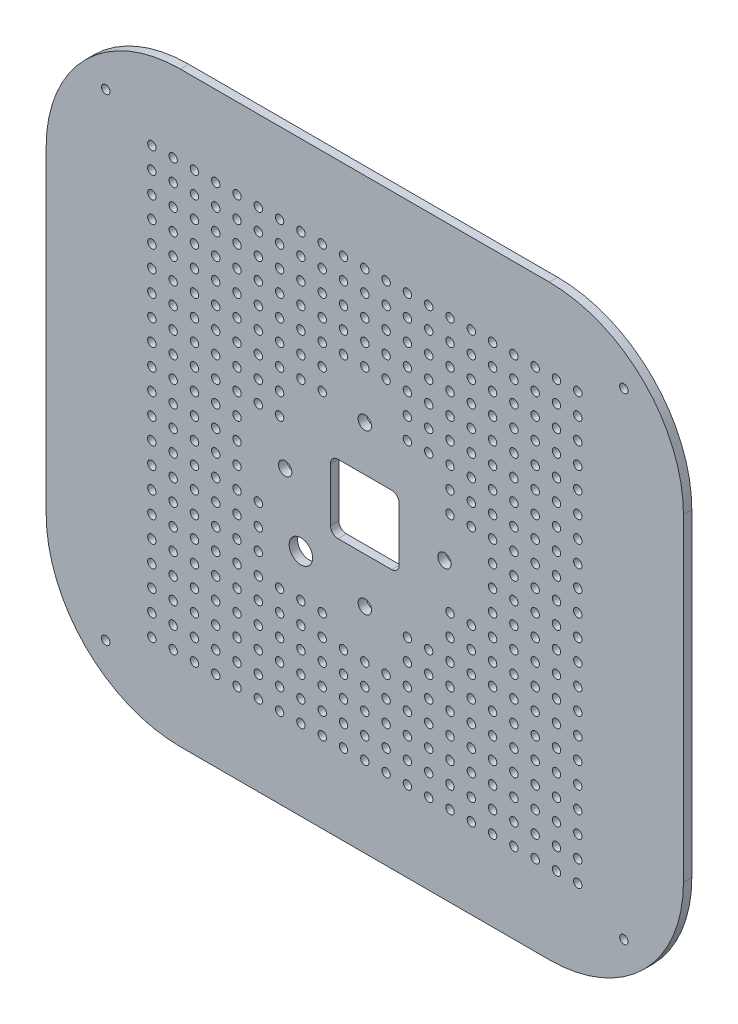
SolidWorks part; units mm, degrees
ref_plane "前视基准面" through (0, 0, 0) normal (0, 0, 1) x (1, 0, 0)
ref_plane "上视基准面" through (0, 0, 0) normal (0, 1, 0) x (1, 0, 0)
ref_plane "右视基准面" through (0, 0, 0) normal (1, 0, 0) x (0, 0, -1)
sketch "草图1" plane through (0, 0, 0) normal (0, 0, 1) x (1, 0, 0)
  line L0 (190, -61.2563) -> (190, 88.7437)
  line L2 (-190, 175) -> (-190, 88.7437)
  line L3 (-190, -175) -> (190, -175)
  line L4 (190, 175) -> (190, 88.7437)
  line L5 (-190, 175) -> (190, -175) construction
  line L6 (-190, -175) -> (190, 175) construction
  line L11 (-190, -61.2563) -> (-190, 88.7437)
  line L12 (-20.5, -20.5) -> (20.5, -20.5)
  line L17 (190, -61.2563) -> (190, -175)
  line L18 (-190, -61.2563) -> (-190, -175)
  line L19 (-20.5, -20.5) -> (-20.5, 20.5)
  line L20 (-20.5, 20.5) -> (20.5, 20.5)
  line L21 (20.5, -20.5) -> (20.5, 20.5)
  line L22 (-20.5, -20.5) -> (20.5, 20.5) construction
  line L23 (-20.5, 20.5) -> (20.5, -20.5) construction
  line L24 (190, 175) -> (-190, 175)
  circle A8 centre (154.4645, 142.2699) radius 2.5
  circle A10 centre (0, 0) radius 210 construction
  circle A13 centre (-154.4645, 142.2699) radius 2.5
  circle A14 centre (-154.4645, -142.2699) radius 2.5
  circle A15 centre (154.4645, -142.2699) radius 2.5
  point P0 (0, 0)
  point P56 (0, 0)
  dimension "D1" = 380
extrude "凸台-拉伸1" add sketch "草图1" along normal blind 5
fillet "圆角1" radius 80 4 edges at (-190, -175, 2.5) (190, -175, 2.5) (-190, 175, 2.5) (190, 175, 2.5)
fillet "圆角3" radius 4.5 4 edges at (-20.5, 20.5, 2.5) (20.5, 20.5, 2.5) (20.5, -20.5, 2.5) (-20.5, -20.5, 2.5)
sketch "草图2" plane through (0, 0, 5) normal (0, 0, 1) x (1, 0, 0)
  circle A0 centre (127, -127) radius 2.5
  circle A1 centre (114.3, -127) radius 2.5
  circle A2 centre (101.6, -127) radius 2.5
  circle A3 centre (88.9, -127) radius 2.5
  circle A4 centre (76.2, -127) radius 2.5
  circle A5 centre (63.5, -127) radius 2.5
  circle A6 centre (50.8, -127) radius 2.5
  circle A7 centre (38.1, -127) radius 2.5
  circle A8 centre (25.4, -127) radius 2.5
  circle A9 centre (12.7, -127) radius 2.5
  circle A10 centre (0, -127) radius 2.5
  circle A11 centre (-12.7, -127) radius 2.5
  circle A12 centre (-25.4, -127) radius 2.5
  circle A13 centre (-38.1, -127) radius 2.5
  circle A14 centre (-50.8, -127) radius 2.5
  circle A15 centre (-63.5, -127) radius 2.5
  circle A16 centre (-76.2, -127) radius 2.5
  circle A17 centre (-88.9, -127) radius 2.5
  circle A18 centre (-101.6, -127) radius 2.5
  circle A19 centre (-114.3, -127) radius 2.5
  circle A20 centre (114.3, -114.3) radius 2.5
  circle A21 centre (101.6, -114.3) radius 2.5
  circle A22 centre (88.9, -114.3) radius 2.5
  circle A23 centre (76.2, -114.3) radius 2.5
  circle A24 centre (63.5, -114.3) radius 2.5
  circle A25 centre (50.8, -114.3) radius 2.5
  circle A26 centre (38.1, -114.3) radius 2.5
  circle A27 centre (25.4, -114.3) radius 2.5
  circle A28 centre (12.7, -114.3) radius 2.5
  circle A29 centre (0, -114.3) radius 2.5
  circle A30 centre (-12.7, -114.3) radius 2.5
  circle A31 centre (-25.4, -114.3) radius 2.5
  circle A32 centre (-38.1, -114.3) radius 2.5
  circle A33 centre (-50.8, -114.3) radius 2.5
  circle A34 centre (-63.5, -114.3) radius 2.5
  circle A35 centre (-76.2, -114.3) radius 2.5
  circle A36 centre (-88.9, -114.3) radius 2.5
  circle A37 centre (-101.6, -114.3) radius 2.5
  circle A38 centre (-114.3, -114.3) radius 2.5
  circle A39 centre (114.3, -101.6) radius 2.5
  circle A40 centre (101.6, -101.6) radius 2.5
  circle A41 centre (88.9, -101.6) radius 2.5
  circle A42 centre (76.2, -101.6) radius 2.5
  circle A43 centre (63.5, -101.6) radius 2.5
  circle A44 centre (50.8, -101.6) radius 2.5
  circle A45 centre (38.1, -101.6) radius 2.5
  circle A46 centre (25.4, -101.6) radius 2.5
  circle A47 centre (12.7, -101.6) radius 2.5
  circle A48 centre (0, -101.6) radius 2.5
  circle A49 centre (-12.7, -101.6) radius 2.5
  circle A50 centre (-25.4, -101.6) radius 2.5
  circle A51 centre (-38.1, -101.6) radius 2.5
  circle A52 centre (-50.8, -101.6) radius 2.5
  circle A53 centre (-63.5, -101.6) radius 2.5
  circle A54 centre (-76.2, -101.6) radius 2.5
  circle A55 centre (-88.9, -101.6) radius 2.5
  circle A56 centre (-101.6, -101.6) radius 2.5
  circle A57 centre (-114.3, -101.6) radius 2.5
  circle A58 centre (114.3, -88.9) radius 2.5
  circle A59 centre (101.6, -88.9) radius 2.5
  circle A60 centre (88.9, -88.9) radius 2.5
  circle A61 centre (76.2, -88.9) radius 2.5
  circle A62 centre (63.5, -88.9) radius 2.5
  circle A63 centre (50.8, -88.9) radius 2.5
  circle A64 centre (38.1, -88.9) radius 2.5
  circle A65 centre (25.4, -88.9) radius 2.5
  circle A66 centre (12.7, -88.9) radius 2.5
  circle A67 centre (0, -88.9) radius 2.5
  circle A68 centre (-12.7, -88.9) radius 2.5
  circle A69 centre (-25.4, -88.9) radius 2.5
  circle A70 centre (-38.1, -88.9) radius 2.5
  circle A71 centre (-50.8, -88.9) radius 2.5
  circle A72 centre (-63.5, -88.9) radius 2.5
  circle A73 centre (-76.2, -88.9) radius 2.5
  circle A74 centre (-88.9, -88.9) radius 2.5
  circle A75 centre (-101.6, -88.9) radius 2.5
  circle A76 centre (-114.3, -88.9) radius 2.5
  circle A77 centre (114.3, -76.2) radius 2.5
  circle A78 centre (101.6, -76.2) radius 2.5
  circle A79 centre (88.9, -76.2) radius 2.5
  circle A80 centre (76.2, -76.2) radius 2.5
  circle A81 centre (63.5, -76.2) radius 2.5
  circle A82 centre (50.8, -76.2) radius 2.5
  circle A83 centre (38.1, -76.2) radius 2.5
  circle A84 centre (25.4, -76.2) radius 2.5
  circle A85 centre (12.7, -76.2) radius 2.5
  circle A86 centre (0, -76.2) radius 2.5
  circle A87 centre (-12.7, -76.2) radius 2.5
  circle A88 centre (-25.4, -76.2) radius 2.5
  circle A89 centre (-38.1, -76.2) radius 2.5
  circle A90 centre (-50.8, -76.2) radius 2.5
  circle A91 centre (-63.5, -76.2) radius 2.5
  circle A92 centre (-76.2, -76.2) radius 2.5
  circle A93 centre (-88.9, -76.2) radius 2.5
  circle A94 centre (-101.6, -76.2) radius 2.5
  circle A95 centre (-114.3, -76.2) radius 2.5
  circle A96 centre (114.3, -63.5) radius 2.5
  circle A97 centre (101.6, -63.5) radius 2.5
  circle A98 centre (88.9, -63.5) radius 2.5
  circle A99 centre (76.2, -63.5) radius 2.5
  circle A100 centre (63.5, -63.5) radius 2.5
  circle A101 centre (50.8, -63.5) radius 2.5
  circle A102 centre (38.1, -63.5) radius 2.5
  circle A103 centre (25.4, -63.5) radius 2.5
  circle A107 centre (-25.4, -63.5) radius 2.5
  circle A108 centre (-38.1, -63.5) radius 2.5
  circle A109 centre (-50.8, -63.5) radius 2.5
  circle A110 centre (-63.5, -63.5) radius 2.5
  circle A111 centre (-76.2, -63.5) radius 2.5
  circle A112 centre (-88.9, -63.5) radius 2.5
  circle A113 centre (-101.6, -63.5) radius 2.5
  circle A114 centre (-114.3, -63.5) radius 2.5
  circle A115 centre (114.3, -50.8) radius 2.5
  circle A116 centre (101.6, -50.8) radius 2.5
  circle A117 centre (88.9, -50.8) radius 2.5
  circle A118 centre (76.2, -50.8) radius 2.5
  circle A119 centre (63.5, -50.8) radius 2.5
  circle A120 centre (50.8, -50.8) radius 2.5
  circle A121 centre (38.1, -50.8) radius 2.5
  circle A122 centre (25.4, -50.8) radius 2.5
  circle A129 centre (-63.5, -50.8) radius 2.5
  circle A130 centre (-76.2, -50.8) radius 2.5
  circle A131 centre (-88.9, -50.8) radius 2.5
  circle A132 centre (-101.6, -50.8) radius 2.5
  circle A133 centre (-114.3, -50.8) radius 2.5
  circle A134 centre (114.3, -38.1) radius 2.5
  circle A135 centre (101.6, -38.1) radius 2.5
  circle A136 centre (88.9, -38.1) radius 2.5
  circle A137 centre (76.2, -38.1) radius 2.5
  circle A138 centre (63.5, -38.1) radius 2.5
  circle A139 centre (50.8, -38.1) radius 2.5
  circle A148 centre (-63.5, -38.1) radius 2.5
  circle A149 centre (-76.2, -38.1) radius 2.5
  circle A150 centre (-88.9, -38.1) radius 2.5
  circle A151 centre (-101.6, -38.1) radius 2.5
  circle A152 centre (-114.3, -38.1) radius 2.5
  circle A153 centre (114.3, -25.4) radius 2.5
  circle A154 centre (101.6, -25.4) radius 2.5
  circle A155 centre (88.9, -25.4) radius 2.5
  circle A156 centre (76.2, -25.4) radius 2.5
  circle A157 centre (63.5, -25.4) radius 2.5
  circle A158 centre (50.8, -25.4) radius 2.5
  circle A167 centre (-63.5, -25.4) radius 2.5
  circle A168 centre (-76.2, -25.4) radius 2.5
  circle A169 centre (-88.9, -25.4) radius 2.5
  circle A170 centre (-101.6, -25.4) radius 2.5
  circle A171 centre (-114.3, -25.4) radius 2.5
  circle A172 centre (114.3, -12.7) radius 2.5
  circle A173 centre (101.6, -12.7) radius 2.5
  circle A174 centre (88.9, -12.7) radius 2.5
  circle A175 centre (76.2, -12.7) radius 2.5
  circle A187 centre (-76.2, -12.7) radius 2.5
  circle A188 centre (-88.9, -12.7) radius 2.5
  circle A189 centre (-101.6, -12.7) radius 2.5
  circle A190 centre (-114.3, -12.7) radius 2.5
  circle A191 centre (114.3, 0) radius 2.5
  circle A192 centre (101.6, 0) radius 2.5
  circle A193 centre (88.9, 0) radius 2.5
  circle A194 centre (76.2, 0) radius 2.5
  circle A206 centre (-76.2, 0) radius 2.5
  circle A207 centre (-88.9, 0) radius 2.5
  circle A208 centre (-101.6, 0) radius 2.5
  circle A209 centre (-114.3, 0) radius 2.5
  circle A210 centre (114.3, 12.7) radius 2.5
  circle A211 centre (101.6, 12.7) radius 2.5
  circle A212 centre (88.9, 12.7) radius 2.5
  circle A213 centre (76.2, 12.7) radius 2.5
  circle A225 centre (-76.2, 12.7) radius 2.5
  circle A226 centre (-88.9, 12.7) radius 2.5
  circle A227 centre (-101.6, 12.7) radius 2.5
  circle A228 centre (-114.3, 12.7) radius 2.5
  circle A229 centre (114.3, 25.4) radius 2.5
  circle A230 centre (101.6, 25.4) radius 2.5
  circle A231 centre (88.9, 25.4) radius 2.5
  circle A232 centre (76.2, 25.4) radius 2.5
  circle A233 centre (63.5, 25.4) radius 2.5
  circle A234 centre (50.8, 25.4) radius 2.5
  circle A242 centre (-50.8, 25.4) radius 2.5
  circle A243 centre (-63.5, 25.4) radius 2.5
  circle A244 centre (-76.2, 25.4) radius 2.5
  circle A245 centre (-88.9, 25.4) radius 2.5
  circle A246 centre (-101.6, 25.4) radius 2.5
  circle A247 centre (-114.3, 25.4) radius 2.5
  circle A248 centre (114.3, 38.1) radius 2.5
  circle A249 centre (101.6, 38.1) radius 2.5
  circle A250 centre (88.9, 38.1) radius 2.5
  circle A251 centre (76.2, 38.1) radius 2.5
  circle A252 centre (63.5, 38.1) radius 2.5
  circle A253 centre (50.8, 38.1) radius 2.5
  circle A261 centre (-50.8, 38.1) radius 2.5
  circle A262 centre (-63.5, 38.1) radius 2.5
  circle A263 centre (-76.2, 38.1) radius 2.5
  circle A264 centre (-88.9, 38.1) radius 2.5
  circle A265 centre (-101.6, 38.1) radius 2.5
  circle A266 centre (-114.3, 38.1) radius 2.5
  circle A267 centre (114.3, 50.8) radius 2.5
  circle A268 centre (101.6, 50.8) radius 2.5
  circle A269 centre (88.9, 50.8) radius 2.5
  circle A270 centre (76.2, 50.8) radius 2.5
  circle A271 centre (63.5, 50.8) radius 2.5
  circle A272 centre (50.8, 50.8) radius 2.5
  circle A273 centre (38.1, 50.8) radius 2.5
  circle A274 centre (25.4, 50.8) radius 2.5
  circle A278 centre (-25.4, 50.8) radius 2.5
  circle A279 centre (-38.1, 50.8) radius 2.5
  circle A280 centre (-50.8, 50.8) radius 2.5
  circle A281 centre (-63.5, 50.8) radius 2.5
  circle A282 centre (-76.2, 50.8) radius 2.5
  circle A283 centre (-88.9, 50.8) radius 2.5
  circle A284 centre (-101.6, 50.8) radius 2.5
  circle A285 centre (-114.3, 50.8) radius 2.5
  circle A286 centre (114.3, 63.5) radius 2.5
  circle A287 centre (101.6, 63.5) radius 2.5
  circle A288 centre (88.9, 63.5) radius 2.5
  circle A289 centre (76.2, 63.5) radius 2.5
  circle A290 centre (63.5, 63.5) radius 2.5
  circle A291 centre (50.8, 63.5) radius 2.5
  circle A292 centre (38.1, 63.5) radius 2.5
  circle A293 centre (25.4, 63.5) radius 2.5
  circle A297 centre (-25.4, 63.5) radius 2.5
  circle A298 centre (-38.1, 63.5) radius 2.5
  circle A299 centre (-50.8, 63.5) radius 2.5
  circle A300 centre (-63.5, 63.5) radius 2.5
  circle A301 centre (-76.2, 63.5) radius 2.5
  circle A302 centre (-88.9, 63.5) radius 2.5
  circle A303 centre (-101.6, 63.5) radius 2.5
  circle A304 centre (-114.3, 63.5) radius 2.5
  circle A305 centre (114.3, 76.2) radius 2.5
  circle A306 centre (101.6, 76.2) radius 2.5
  circle A307 centre (88.9, 76.2) radius 2.5
  circle A308 centre (76.2, 76.2) radius 2.5
  circle A309 centre (63.5, 76.2) radius 2.5
  circle A310 centre (50.8, 76.2) radius 2.5
  circle A311 centre (38.1, 76.2) radius 2.5
  circle A312 centre (25.4, 76.2) radius 2.5
  circle A313 centre (12.7, 76.2) radius 2.5
  circle A314 centre (0, 76.2) radius 2.5
  circle A315 centre (-12.7, 76.2) radius 2.5
  circle A316 centre (-25.4, 76.2) radius 2.5
  circle A317 centre (-38.1, 76.2) radius 2.5
  circle A318 centre (-50.8, 76.2) radius 2.5
  circle A319 centre (-63.5, 76.2) radius 2.5
  circle A320 centre (-76.2, 76.2) radius 2.5
  circle A321 centre (-88.9, 76.2) radius 2.5
  circle A322 centre (-101.6, 76.2) radius 2.5
  circle A323 centre (-114.3, 76.2) radius 2.5
  circle A324 centre (114.3, 88.9) radius 2.5
  circle A325 centre (101.6, 88.9) radius 2.5
  circle A326 centre (88.9, 88.9) radius 2.5
  circle A327 centre (76.2, 88.9) radius 2.5
  circle A328 centre (63.5, 88.9) radius 2.5
  circle A329 centre (50.8, 88.9) radius 2.5
  circle A330 centre (38.1, 88.9) radius 2.5
  circle A331 centre (25.4, 88.9) radius 2.5
  circle A332 centre (12.7, 88.9) radius 2.5
  circle A333 centre (0, 88.9) radius 2.5
  circle A334 centre (-12.7, 88.9) radius 2.5
  circle A335 centre (-25.4, 88.9) radius 2.5
  circle A336 centre (-38.1, 88.9) radius 2.5
  circle A337 centre (-50.8, 88.9) radius 2.5
  circle A338 centre (-63.5, 88.9) radius 2.5
  circle A339 centre (-76.2, 88.9) radius 2.5
  circle A340 centre (-88.9, 88.9) radius 2.5
  circle A341 centre (-101.6, 88.9) radius 2.5
  circle A342 centre (-114.3, 88.9) radius 2.5
  circle A343 centre (114.3, 101.6) radius 2.5
  circle A344 centre (101.6, 101.6) radius 2.5
  circle A345 centre (88.9, 101.6) radius 2.5
  circle A346 centre (76.2, 101.6) radius 2.5
  circle A347 centre (63.5, 101.6) radius 2.5
  circle A348 centre (50.8, 101.6) radius 2.5
  circle A349 centre (38.1, 101.6) radius 2.5
  circle A350 centre (25.4, 101.6) radius 2.5
  circle A351 centre (12.7, 101.6) radius 2.5
  circle A352 centre (0, 101.6) radius 2.5
  circle A353 centre (-12.7, 101.6) radius 2.5
  circle A354 centre (-25.4, 101.6) radius 2.5
  circle A355 centre (-38.1, 101.6) radius 2.5
  circle A356 centre (-50.8, 101.6) radius 2.5
  circle A357 centre (-63.5, 101.6) radius 2.5
  circle A358 centre (-76.2, 101.6) radius 2.5
  circle A359 centre (-88.9, 101.6) radius 2.5
  circle A360 centre (-101.6, 101.6) radius 2.5
  circle A361 centre (-114.3, 101.6) radius 2.5
  circle A362 centre (114.3, 114.3) radius 2.5
  circle A363 centre (101.6, 114.3) radius 2.5
  circle A364 centre (88.9, 114.3) radius 2.5
  circle A365 centre (76.2, 114.3) radius 2.5
  circle A366 centre (63.5, 114.3) radius 2.5
  circle A367 centre (50.8, 114.3) radius 2.5
  circle A368 centre (38.1, 114.3) radius 2.5
  circle A369 centre (25.4, 114.3) radius 2.5
  circle A370 centre (12.7, 114.3) radius 2.5
  circle A371 centre (0, 114.3) radius 2.5
  circle A372 centre (-12.7, 114.3) radius 2.5
  circle A373 centre (-25.4, 114.3) radius 2.5
  circle A374 centre (-38.1, 114.3) radius 2.5
  circle A375 centre (-50.8, 114.3) radius 2.5
  circle A376 centre (-63.5, 114.3) radius 2.5
  circle A377 centre (-76.2, 114.3) radius 2.5
  circle A378 centre (-88.9, 114.3) radius 2.5
  circle A379 centre (-101.6, 114.3) radius 2.5
  circle A380 centre (-114.3, 114.3) radius 2.5
  circle A381 centre (127, -114.3) radius 2.5
  circle A382 centre (127, -101.6) radius 2.5
  circle A383 centre (127, -88.9) radius 2.5
  circle A384 centre (127, -76.2) radius 2.5
  circle A385 centre (127, -63.5) radius 2.5
  circle A386 centre (127, -50.8) radius 2.5
  circle A387 centre (127, -38.1) radius 2.5
  circle A388 centre (127, -25.4) radius 2.5
  circle A389 centre (127, -12.7) radius 2.5
  circle A390 centre (127, 0) radius 2.5
  circle A391 centre (127, 12.7) radius 2.5
  circle A392 centre (127, 25.4) radius 2.5
  circle A393 centre (127, 38.1) radius 2.5
  circle A394 centre (127, 50.8) radius 2.5
  circle A395 centre (127, 63.5) radius 2.5
  circle A396 centre (127, 76.2) radius 2.5
  circle A397 centre (127, 88.9) radius 2.5
  circle A398 centre (127, 101.6) radius 2.5
  circle A399 centre (127, 114.3) radius 2.5
  circle A400 centre (127, 127) radius 2.5
  circle A401 centre (114.3, 127) radius 2.5
  circle A402 centre (101.6, 127) radius 2.5
  circle A403 centre (88.9, 127) radius 2.5
  circle A404 centre (76.2, 127) radius 2.5
  circle A405 centre (63.5, 127) radius 2.5
  circle A406 centre (50.8, 127) radius 2.5
  circle A407 centre (38.1, 127) radius 2.5
  circle A408 centre (25.4, 127) radius 2.5
  circle A409 centre (12.7, 127) radius 2.5
  circle A410 centre (0, 127) radius 2.5
  circle A411 centre (-12.7, 127) radius 2.5
  circle A412 centre (-25.4, 127) radius 2.5
  circle A413 centre (-38.1, 127) radius 2.5
  circle A414 centre (-50.8, 127) radius 2.5
  circle A415 centre (-63.5, 127) radius 2.5
  circle A416 centre (-76.2, 127) radius 2.5
  circle A417 centre (-88.9, 127) radius 2.5
  circle A418 centre (-101.6, 127) radius 2.5
  circle A419 centre (-114.3, 127) radius 2.5
  circle A420 centre (-127, -127) radius 2.5
  circle A421 centre (-127, -114.3) radius 2.5
  circle A422 centre (-127, -101.6) radius 2.5
  circle A423 centre (-127, -88.9) radius 2.5
  circle A424 centre (-127, -76.2) radius 2.5
  circle A425 centre (-127, -63.5) radius 2.5
  circle A426 centre (-127, -50.8) radius 2.5
  circle A427 centre (-127, -38.1) radius 2.5
  circle A428 centre (-127, -25.4) radius 2.5
  circle A429 centre (-127, -12.7) radius 2.5
  circle A430 centre (-127, 0) radius 2.5
  circle A431 centre (-127, 12.7) radius 2.5
  circle A432 centre (-127, 25.4) radius 2.5
  circle A433 centre (-127, 38.1) radius 2.5
  circle A434 centre (-127, 50.8) radius 2.5
  circle A435 centre (-127, 63.5) radius 2.5
  circle A436 centre (-127, 76.2) radius 2.5
  circle A437 centre (-127, 88.9) radius 2.5
  circle A438 centre (-127, 101.6) radius 2.5
  circle A439 centre (-127, 114.3) radius 2.5
  circle A440 centre (-127, 127) radius 2.5
  circle A441 centre (38.1, -38.1) radius 2.5 [skipped]
  circle A442 centre (25.4, -38.1) radius 2.5 [skipped]
  circle A443 centre (12.7, -38.1) radius 2.5 [skipped]
  circle A444 centre (0, -38.1) radius 2.5 [skipped]
  circle A445 centre (-12.7, -38.1) radius 2.5 [skipped]
  circle A446 centre (-25.4, -38.1) radius 2.5 [skipped]
  circle A447 centre (-38.1, -38.1) radius 2.5 [skipped]
  circle A448 centre (38.1, -25.4) radius 2.5 [skipped]
  circle A449 centre (25.4, -25.4) radius 2.5 [skipped]
  circle A450 centre (12.7, -25.4) radius 2.5 [skipped]
  circle A451 centre (0, -25.4) radius 2.5 [skipped]
  circle A452 centre (-12.7, -25.4) radius 2.5 [skipped]
  circle A453 centre (-25.4, -25.4) radius 2.5 [skipped]
  circle A454 centre (-38.1, -25.4) radius 2.5 [skipped]
  circle A455 centre (38.1, -12.7) radius 2.5 [skipped]
  circle A456 centre (25.4, -12.7) radius 2.5 [skipped]
  circle A457 centre (12.7, -12.7) radius 2.5 [skipped]
  circle A458 centre (0, -12.7) radius 2.5 [skipped]
  circle A459 centre (-12.7, -12.7) radius 2.5 [skipped]
  circle A460 centre (-25.4, -12.7) radius 2.5 [skipped]
  circle A461 centre (-38.1, -12.7) radius 2.5 [skipped]
  circle A462 centre (38.1, 0) radius 2.5 [skipped]
  circle A463 centre (25.4, 0) radius 2.5 [skipped]
  circle A464 centre (12.7, 0) radius 2.5 [skipped]
  circle A465 centre (0, 0) radius 2.5 [skipped]
  circle A466 centre (-12.7, 0) radius 2.5 [skipped]
  circle A467 centre (-25.4, 0) radius 2.5 [skipped]
  circle A468 centre (-38.1, 0) radius 2.5 [skipped]
  circle A469 centre (38.1, 12.7) radius 2.5 [skipped]
  circle A470 centre (25.4, 12.7) radius 2.5 [skipped]
  circle A471 centre (12.7, 12.7) radius 2.5 [skipped]
  circle A472 centre (0, 12.7) radius 2.5 [skipped]
  circle A473 centre (-12.7, 12.7) radius 2.5 [skipped]
  circle A474 centre (-25.4, 12.7) radius 2.5 [skipped]
  circle A475 centre (-38.1, 12.7) radius 2.5 [skipped]
  circle A476 centre (38.1, 25.4) radius 2.5 [skipped]
  circle A477 centre (25.4, 25.4) radius 2.5 [skipped]
  circle A478 centre (12.7, 25.4) radius 2.5 [skipped]
  circle A479 centre (0, 25.4) radius 2.5 [skipped]
  circle A480 centre (-12.7, 25.4) radius 2.5 [skipped]
  circle A481 centre (-25.4, 25.4) radius 2.5 [skipped]
  circle A482 centre (-38.1, 25.4) radius 2.5 [skipped]
  circle A483 centre (38.1, 38.1) radius 2.5 [skipped]
  circle A484 centre (25.4, 38.1) radius 2.5 [skipped]
  circle A485 centre (12.7, 38.1) radius 2.5 [skipped]
  circle A486 centre (0, 38.1) radius 2.5 [skipped]
  circle A487 centre (-12.7, 38.1) radius 2.5 [skipped]
  circle A488 centre (-25.4, 38.1) radius 2.5 [skipped]
  circle A489 centre (-38.1, 38.1) radius 2.5 [skipped]
  circle A491 centre (12.7, -50.8) radius 2.5 [skipped]
  circle A492 centre (0, -50.8) radius 2.5 [skipped]
  circle A493 centre (-12.7, -50.8) radius 2.5 [skipped]
  circle A494 centre (50.8, -12.7) radius 2.5 [skipped]
  circle A495 centre (50.8, 0) radius 2.5 [skipped]
  circle A496 centre (50.8, 12.7) radius 2.5 [skipped]
  circle A497 centre (12.7, 50.8) radius 2.5 [skipped]
  circle A498 centre (0, 50.8) radius 2.5 [skipped]
  circle A499 centre (-12.7, 50.8) radius 2.5 [skipped]
  circle A500 centre (-50.8, -12.7) radius 2.5 [skipped]
  circle A501 centre (-50.8, 0) radius 2.5 [skipped]
  circle A502 centre (-50.8, 12.7) radius 2.5 [skipped]
  circle A503 centre (0, -47.5) radius 4
  circle A504 centre (-47.5, 0) radius 4
  circle A505 centre (0, 47.5) radius 4
  circle A506 centre (47.5, 0) radius 4
  circle A507 centre (0, -63.5) radius 2.5 [skipped]
  circle A508 centre (-12.7, -63.5) radius 2.5 [skipped]
  circle A509 centre (63.5, -12.7) radius 2.5 [skipped]
  circle A510 centre (63.5, 0) radius 2.5 [skipped]
  circle A511 centre (63.5, 12.7) radius 2.5 [skipped]
  circle A512 centre (12.7, 63.5) radius 2.5 [skipped]
  circle A513 centre (0, 63.5) radius 2.5 [skipped]
  circle A514 centre (-12.7, 63.5) radius 2.5 [skipped]
  circle A515 centre (-63.5, -12.7) radius 2.5 [skipped]
  circle A516 centre (-63.5, 0) radius 2.5 [skipped]
  circle A517 centre (-63.5, 12.7) radius 2.5 [skipped]
  circle A518 centre (12.7, -63.5) radius 2.5 [skipped]
  circle A519 centre (-25.4, -50.8) radius 2.5 [skipped]
  circle A520 centre (-38.1, -50.8) radius 2.5 [skipped]
  circle A521 centre (-50.8, -50.8) radius 2.5 [skipped]
  circle A522 centre (-50.8, -38.1) radius 2.5 [skipped]
  circle A523 centre (-50.8, -25.4) radius 2.5 [skipped]
  circle A524 centre (-38.1, -38.1) radius 7
  point P287 (0, 0)
  dimension "D1" = 21
  dimension "D3" = 4
  dimension "D2" = 21
extrude "切除-拉伸1" cut sketch "草图2" against normal blind 10
